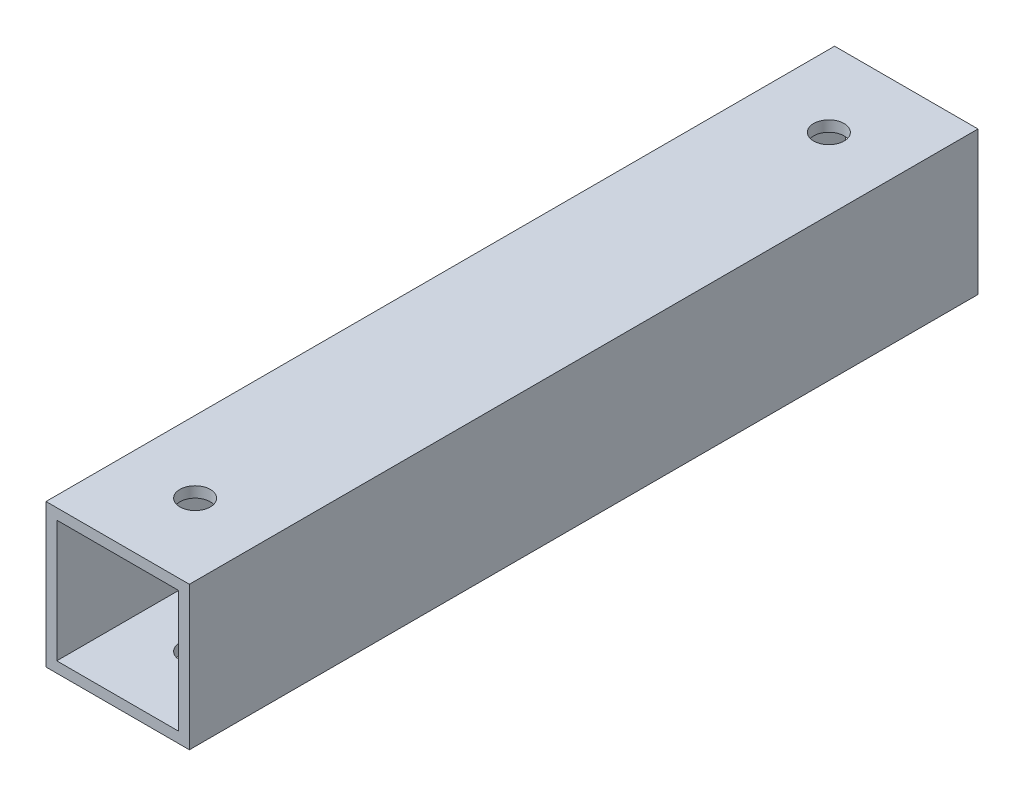
SolidWorks part; units mm, degrees
ref_plane "Front Plane" through (0, 0, 0) normal (0, 0, 1) x (1, 0, 0)
ref_plane "Top Plane" through (0, 0, 0) normal (0, 1, 0) x (1, 0, 0)
ref_plane "Right Plane" through (0, 0, 0) normal (1, 0, 0) x (0, 0, -1)
sketch "Sketch1" plane through (0, 0, 0) normal (0, 0, 1) x (1, 0, 0)
  line L0 (-8.5, -8.5) -> (8.5, -8.5)
  line L1 (-10, -10) -> (10, -10)
  line L2 (-10, -10) -> (-10, 10)
  line L3 (-10, 10) -> (10, 10)
  line L4 (10, -10) -> (10, 10)
  line L5 (-10, -10) -> (10, 10) construction
  line L6 (-10, 10) -> (10, -10) construction
  line L7 (8.5, -8.5) -> (8.5, 8.5)
  line L8 (-8.5, 8.5) -> (8.5, 8.5)
  line L9 (-8.5, -8.5) -> (-8.5, 8.5)
  point P0 (0, 0)
  dimension "D1" = 20
  dimension "D3" = 20
  dimension "D2" = 1.5
extrude "Boss-Extrude1" add sketch "Sketch1" against normal blind 110
sketch "Sketch2" plane through (0, 10, 0) normal (0, 1, 0) x (1, 0, 0)
  line L0 (10, 0) -> (-10, 0) construction
  line L1 (-10, 55) -> (10, 55) construction
  line L2 (-10, 110) -> (-10, 0) construction
  line L3 (10, 110) -> (10, 0) construction
  circle A0 centre (0, 10.8) radius 2.125
  circle A1 centre (0, 99.2) radius 2.125
  dimension "D1" = 4.25
  dimension "D2" = 10.8
extrude "Cut-Extrude1" cut sketch "Sketch2" against normal through all
